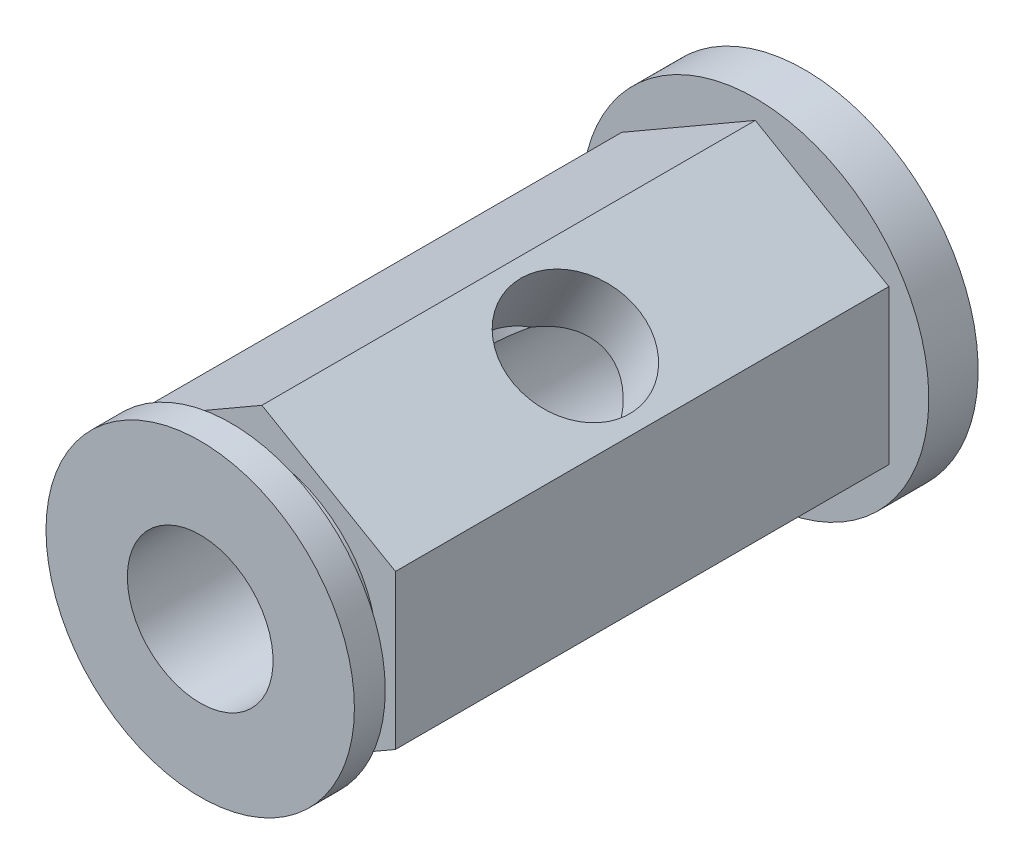
SolidWorks part; units mm, degrees
material "AISI 1020"
ref_plane "Front Plane" through (0, 0, 0) normal (0, 0, 1) x (1, 0, 0)
ref_plane "Top Plane" through (0, 0, 0) normal (0, 1, 0) x (1, 0, 0)
ref_plane "Right Plane" through (0, 0, 0) normal (1, 0, 0) x (0, 0, -1)
sketch "Sketch1" plane through (0, 0, 0) normal (0, 0, 1) x (1, 0, 0)
  line L1 (0, 6.35) -> (-5.4993, 3.175)
  line L2 (-5.4993, 3.175) -> (-5.4993, -3.175)
  line L3 (-5.4993, -3.175) -> (0, -6.35)
  line L4 (0, -6.35) -> (5.4993, -3.175)
  line L5 (5.4993, -3.175) -> (5.4993, 3.175)
  line L6 (5.4993, 3.175) -> (0, 6.35)
  circle A0 centre (0, 0) radius 6.35 construction
  dimension "D1" = 12.7
extrude "Boss-Extrude1" add sketch "Sketch1" along normal blind 20.32
sketch "Sketch2" plane through (0, 0, 0) normal (0, 0, -1) x (-1, 0, 0)
  circle A0 centre (0, 0) radius 7.1438
  dimension "D1" = 14.2875
extrude "Boss-Extrude2" add sketch "Sketch2" along normal blind 2.032
sketch "Sketch3" plane through (0, 0, 20.32) normal (0, 0, 1) x (1, 0, 0)
  circle A0 centre (0, 0) radius 4.7386
extrude "Boss-Extrude3" add sketch "Sketch3" along normal blind 1.27
sketch "Sketch4" plane through (0, 0, 21.59) normal (0, 0, 1) x (1, 0, 0)
  circle A0 centre (0, 0) radius 6.35
  dimension "D1" = 12.7
extrude "Boss-Extrude4" add sketch "Sketch4" along normal blind 1.27
sketch "Sketch5" plane through (0, 0, -2.032) normal (0, 0, -1) x (-1, 0, 0)
  circle A0 centre (0, 0) radius 3
  dimension "D1" = 6
extrude "Cut-Extrude1" cut sketch "Sketch5" against normal through all
sketch "Sketch6" plane through (2.7496, 4.7625, 0) normal (0.5, 0.866, 0) x (0.866, -0.5, 0)
  line L0 (0, 0) -> (0, -20.32) construction
  line L1 (3.175, 0) -> (-3.175, 0) construction
  line L2 (3.175, -20.32) -> (-3.175, -20.32) construction
  point P6 (0, -10.16)
hole_wizard "#6 (0.204) Diameter Hole1" positions "Sketch10" profile "Sketch9" hole size "#6" standard "ANSI Inch"
sketch "Sketch10" plane through (2.7496, 4.7625, 0) normal (0.5, 0.866, 0) x (0.866, -0.5, 0)
  point P0 (0, -10.16)
sketch "Sketch9" plane through (2.7496, 4.7625, 10.16) normal (0, 0, 1) x (-0.866, 0.5, 0)
  line L0 (0, 0) -> (0, 4.8587)
  line L1 (0, 4.8587) -> (2.5908, 3.302)
  line L2 (2.5908, 3.302) -> (2.5908, 0)
  line L5 (2.5908, 0) -> (0, 0)
  line L10 (0, 4.8587) -> (-2.5908, 3.302) construction
  line L11 (0, -6.35) -> (0, 107.95) construction
  dimension "Hole Dia." = 5.1816
  dimension "Hole Depth" = 3.302
  dimension "Drill Angle" = 118
